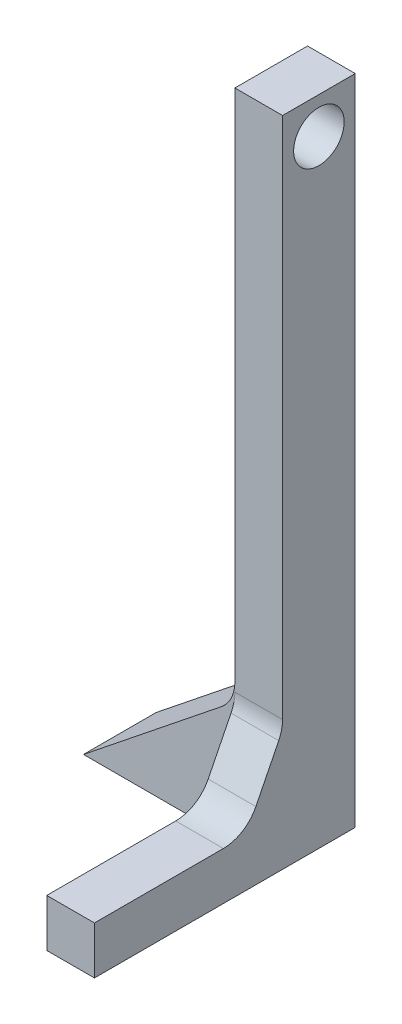
SolidWorks part; units mm, degrees
ref_plane "Front Plane" through (0, 0, 0) normal (0, 0, 1) x (1, 0, 0)
ref_plane "Top Plane" through (0, 0, 0) normal (0, 1, 0) x (1, 0, 0)
ref_plane "Right Plane" through (0, 0, 0) normal (1, 0, 0) x (0, 0, -1)
ref_plane "Plane1" through (37.7307, 0, 0) normal (1, 0, 0) x (0, 0, -1)
sketch "Sketch1" plane through (37.7307, 0, 0) normal (1, 0, 0) x (0, 0, -1)
  line L0 (136.3281, 49.8362) -> (128.7081, 49.8362) construction
  line L1 (128.7081, 57.4562) -> (143.9481, 57.4562)
  line L2 (128.7081, 57.4562) -> (128.7081, -79.4588)
  line L3 (128.7081, -79.4588) -> (143.9481, -79.4588)
  line L4 (143.9481, 57.4562) -> (143.9481, -79.4588)
  line L5 (136.3281, 49.8362) -> (143.9481, 49.8362) construction
  line L6 (136.3281, 49.8362) -> (136.3281, 57.4562) construction
  line L7 (46.8209, -79.4588) -> (-104.9719, -79.4588) construction
  dimension "D1" = 15.24
extrude "Boss-Extrude1" add sketch "Sketch1" along normal blind 10
sketch "Sketch2" plane through (47.7307, 0, 0) normal (1, 0, 0) x (0, 0, -1)
  circle A0 centre (136.3281, 49.8362) radius 5.3
  dimension "D1" = 10.6
extrude "Cut-Extrude1" cut sketch "Sketch2" against normal through all
sketch "Sketch4" plane through (0, 0, -143.9481) normal (0, 0, -1) x (-1, 0, 0)
  line L0 (-37.7307, -79.4588) -> (-5.9807, -79.4588)
  line L1 (-5.9807, -79.4588) -> (-37.7307, -54.0588)
  line L2 (-37.7307, -79.4588) -> (-37.7307, 57.4562) construction
  line L3 (-37.7307, -54.0588) -> (-37.7307, -79.4588)
  dimension "D1" = 31.75
  dimension "D3" = 25.4
extrude "Boss-Extrude2" add sketch "Sketch4" against normal up to surface (15.24 mm away) up to face at (42.7307, -11.0013, -128.7081)
sketch "Sketch6" plane through (47.7307, 0, 0) normal (1, 0, 0) x (0, 0, -1)
  line L0 (128.7081, -79.4588) -> (116.0081, -79.4588)
  line L1 (121.0081, -69.4588) -> (128.7081, -54.0588)
  line L2 (128.7081, 57.4562) -> (128.7081, -79.4588) construction
  line L3 (116.0081, -79.4588) -> (89.2581, -79.4588)
  line L4 (89.2581, -79.4588) -> (89.2581, -69.4588)
  line L5 (89.2581, -69.4588) -> (121.0081, -69.4588)
  line L6 (121.0081, -69.4588) -> (116.0081, -79.4588) construction
  line L8 (128.7081, -54.0588) -> (128.7081, -79.4588)
  point P9 (0, 0)
  point P10 (0, 0)
  point P11 (0, 0)
  dimension "D1" = 12.7
  dimension "D2" = 10
  dimension "D3" = 31.75
extrude "Boss-Extrude3" add sketch "Sketch6" against normal up to surface (10 mm away) up to face at (37.7307, 49.8362, -141.6281)
fillet "Fillet7" radius 7.62 2 edges at (42.7307, -69.4588, -121.0081) (37.7307, -54.0588, -136.3281)
fillet "Fillet8" radius 7.62 1 edges at (42.7307, -54.0588, -128.7081)
